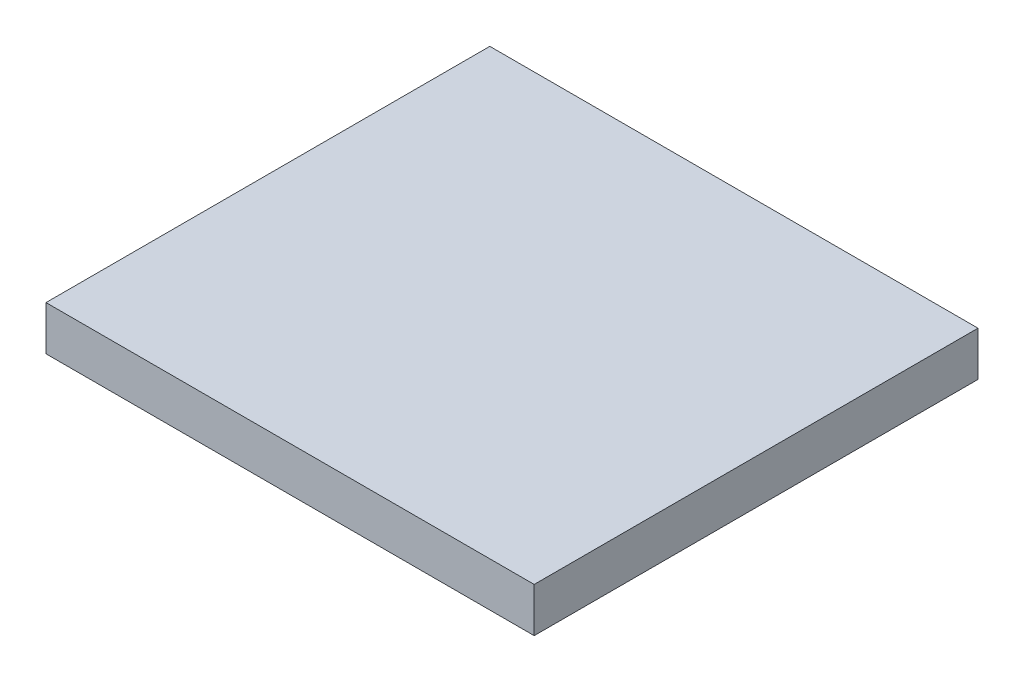
SolidWorks part; units mm, degrees
material "Copper"
ref_plane "Front Plane" through (0, 0, 0) normal (0, 0, 1) x (1, 0, 0)
ref_plane "Top Plane" through (0, 0, 0) normal (0, 1, 0) x (1, 0, 0)
ref_plane "Right Plane" through (0, 0, 0) normal (1, 0, 0) x (0, 0, -1)
sketch "Sketch1" plane through (0, 0, 0) normal (0, 1, 0) x (1, 0, 0)
  line L1 (110, -100) -> (-110, -100)
  line L2 (110, -100) -> (110, 100)
  line L3 (110, 100) -> (-110, 100)
  line L4 (-110, -100) -> (-110, 100)
  line L5 (110, -100) -> (-110, 100) construction
  line L6 (110, 100) -> (-110, -100) construction
  point P0 (0, 0)
  dimension "D1" = 200
  dimension "D2" = 220
extrude "Boss-Extrude1" add sketch "Sketch1" along normal blind 20
